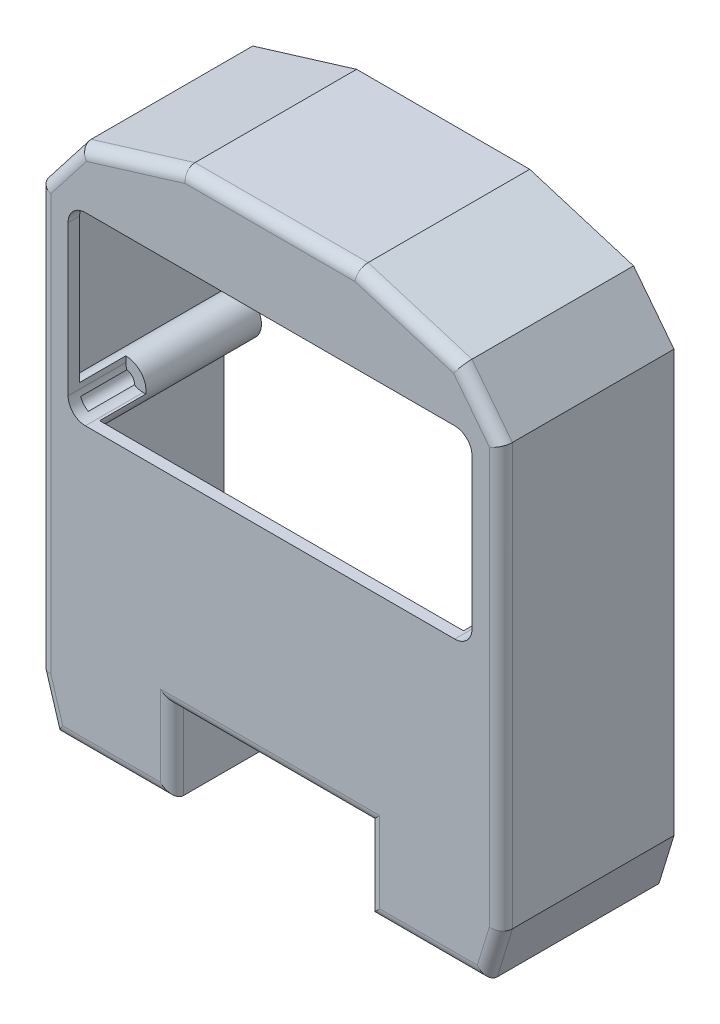
SolidWorks part; units mm, degrees
ref_plane "前视基准面" through (0, 0, 0) normal (0, 0, 1) x (1, 0, 0)
ref_plane "上视基准面" through (0, 0, 0) normal (0, 1, 0) x (1, 0, 0)
ref_plane "右视基准面" through (0, 0, 0) normal (1, 0, 0) x (0, 0, -1)
sketch "草图1" plane through (0, 0, 0) normal (0, 0, 1) x (1, 0, 0)
  line L0 (-84.4028, 44) -> (-87, 52.5)
  line L1 (-78.4444, 24.5) -> (-87, 52.5) construction
  line L2 (-87, 52.5) -> (-87, 125.5)
  line L3 (-87, 125.5) -> (-80, 134.5)
  line L5 (-80, 134.5) -> (-62, 140)
  line L6 (-62, 140) -> (-32, 140)
  line L7 (-32, 140) -> (-14, 134.5)
  line L8 (-14, 134.5) -> (-7, 125.5)
  line L9 (-7, 125.5) -> (-7, 52.5)
  line L10 (-7, 52.5) -> (-15.5556, 24.5) construction
  line L11 (-7, 125.5) -> (-7, 52.5) construction
  line L12 (-7, 52.5) -> (-9.5972, 44)
  line L13 (-9.5972, 44) -> (-30, 44)
  line L14 (-30, 44) -> (-30, 58)
  line L15 (-30, 58) -> (-64, 58)
  line L16 (-64, 58) -> (-64, 44)
  line L17 (-64, 44) -> (-84.4028, 44)
  dimension "D1" = 14
  dimension "D2" = 3
  dimension "D3" = 34
extrude "凸台-拉伸1" add sketch "草图1" along normal blind 30
fillet "圆角4" radius 2 14 edges at (-23, 137.25, 30) (-85.7014, 48.25, 30) (-87, 89, 30) (-83.5, 130, 30) (-71, 137.25, 30) (-47, 140, 30) (-10.5, 130, 30) (-7, 89, 30) (-8.2986, 48.25, 30) (-19.7986, 44, 30) (-30, 51, 30) (-47, 58, 30) (-64, 51, 30) (-74.2014, 44, 30)
sketch "草图2" plane through (0, 0, 0) normal (0, 0, -1) x (-1, 0, 0)
  circle A0 centre (82, 53.5) radius 1.5
  circle A1 centre (12, 53.5) radius 1.5
  circle A2 centre (12, 93.5) radius 1.5
  circle A3 centre (82, 93.5) radius 1.5
  circle A4 centre (78, 129.5) radius 1.5
  circle A5 centre (16, 129.5) radius 1.5
extrude "切除-拉伸1" cut sketch "草图2" against normal offset from surface (28 mm away) 2 up to face at (-47, 85.7693, 30)
shell "抽壳3" thickness 2 removed face at (-13.5, 53.5, 0)
sketch "草图3" plane through (0, 0, 30) normal (0, 0, 1) x (1, 0, 0)
  line L0 (-47, 125) -> (-47, 138) construction
  line L1 (-79, 125) -> (-15, 125)
  line L2 (-82, 122) -> (-82, 96)
  line L3 (-79, 93) -> (-15, 93)
  line L4 (-12, 122) -> (-12, 96)
  line L5 (-32.2987, 138) -> (-61.7013, 138) construction
  arc A0 (-15, 125) -> (-12, 122) centre (-15, 122) cw
  arc A1 (-15, 93) -> (-12, 96) centre (-15, 96) ccw
  arc A2 (-82, 96) -> (-79, 93) centre (-79, 96) ccw
  arc A3 (-79, 125) -> (-82, 122) centre (-79, 122) ccw
  point P6 (-12, 125)
  point P15 (-82, 93)
  point P18 (-82, 125)
  dimension "D4" = 3
  dimension "D1" = 32
  dimension "D2" = 70
  dimension "D3" = 13
extrude "切除-拉伸2" cut sketch "草图3" against normal blind 10
